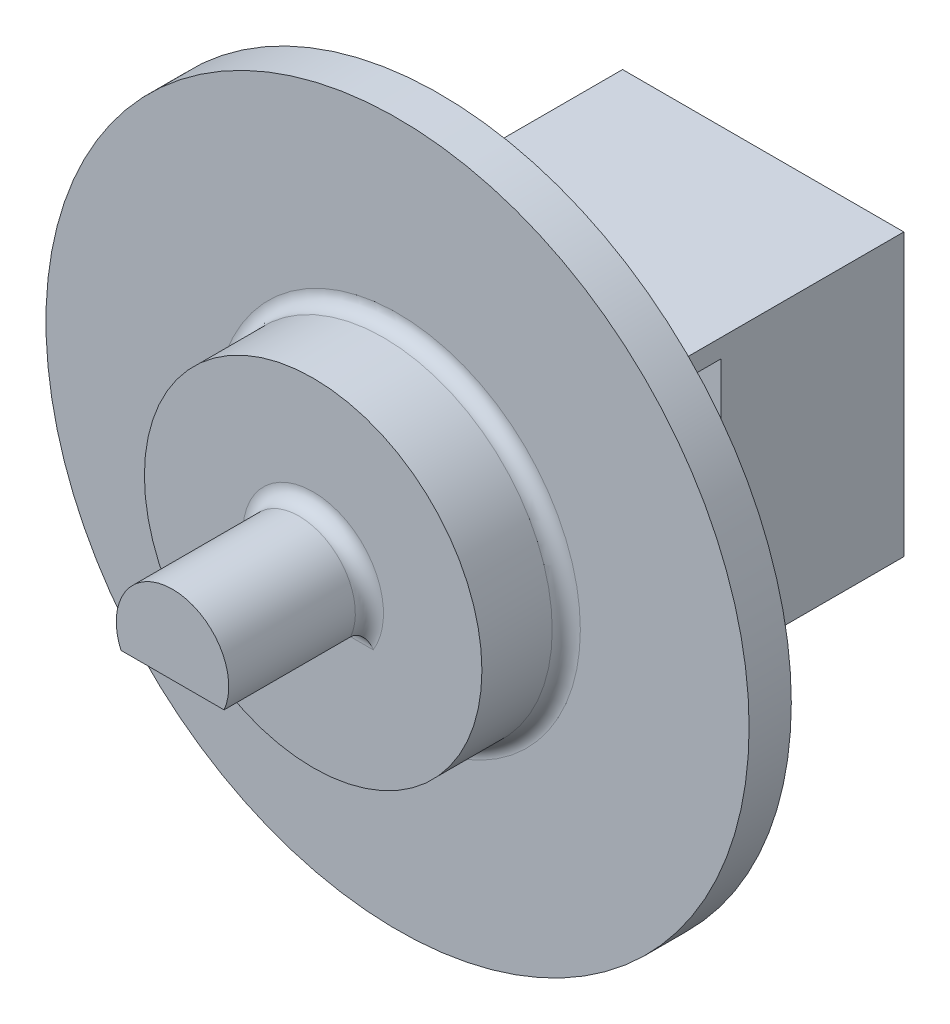
SolidWorks part; units mm, degrees
ref_plane "Front Plane" through (0, 0, 0) normal (0, 0, 1) x (1, 0, 0)
ref_plane "Top Plane" through (0, 0, 0) normal (0, 1, 0) x (1, 0, 0)
ref_plane "Right Plane" through (0, 0, 0) normal (1, 0, 0) x (0, 0, -1)
sketch "Sketch3" plane through (0, 0, 0) normal (0, 0, 1) x (1, 0, 0)
  line L0 (0.8667, 3.2345) -> (0.8667, 5) construction
  line L1 (-5, -5) -> (5, -5)
  line L2 (-5, -5) -> (-5, 5)
  line L3 (-5, 5) -> (5, 5)
  line L4 (5, -5) -> (5, 5)
  line L5 (-5, -5) -> (5, 5) construction
  line L6 (-5, 5) -> (5, -5) construction
  line L7 (3.2345, 0.8667) -> (0.8667, 3.2345)
  line L8 (0.8667, 3.2345) -> (-2.3678, 2.3678)
  line L9 (-2.3678, 2.3678) -> (-3.2345, -0.8667)
  line L10 (-3.2345, -0.8667) -> (-0.8667, -3.2345)
  line L11 (-0.8667, -3.2345) -> (2.3678, -2.3678)
  line L12 (2.3678, -2.3678) -> (3.2345, 0.8667)
  line L13 (3.2345, 0.8667) -> (5, 0.8667) construction
  circle A0 centre (0, 0) radius 1.75
  circle A2 centre (0, 0) radius 2.9 construction
  point P0 (0, 0)
  dimension "D2" = 3.5
  dimension "D3" = 5.8
  dimension "D1" = 10
extrude "Boss-Extrude4" add sketch "Sketch3" along normal blind 11.5 contours L1 L4 L3 L2 | A0 region at (-4.8586, 0, 0) region at (2.7128, -0.7269, 0)
extrude "Cut-Extrude1" cut sketch "Sketch3<3>" against normal blind 5 from surface contours A0 region at (2.7128, -0.7269, 0) starting at face at (0, 0, 11.5)
sketch "Sketch3<3>" plane through (0, 0, 0) normal (0, 0, 1) x (1, 0, 0) same geometry as "Sketch3"
sketch "Sketch4" plane through (0, 0, 11.5) normal (0, 0, 1) x (1, 0, 0)
  line L1 (3.2345, 0.8667) -> (0.8667, 3.2345)
  line L2 (0.8667, 3.2345) -> (-2.3678, 2.3678)
  line L3 (-2.3678, 2.3678) -> (-3.2345, -0.8667)
  line L4 (-3.2345, -0.8667) -> (-0.8667, -3.2345)
  line L5 (-0.8667, -3.2345) -> (2.3678, -2.3678)
  line L6 (2.3678, -2.3678) -> (3.2345, 0.8667)
  circle A0 centre (0, 0) radius 12.5
  circle A3 centre (0, 0) radius 2.9 construction
  dimension "D1" = 25
extrude "Boss-Extrude5" add sketch "Sketch4" along normal blind 1.5
ref_plane "Plane1" through (1.6173, 0.4333, 0) normal (0.9659, 0.2588, 0) x (0, 0, -1)
sketch "Sketch5" plane through (2.9287, -4.4609, 0) normal (0.9659, 0.2588, 0) x (0, 0, 1)
  line L1 (6.5, -7.9669) -> (11.5, -7.9669)
  line L2 (6.5, -7.9669) -> (6.5, -2.1669)
  line L3 (6.5, -2.1669) -> (11.5, -2.1669)
  line L4 (11.5, -7.9669) -> (11.5, -2.1669)
  line L5 (6.5, -7.9669) -> (11.5, -2.1669) construction
  line L6 (6.5, -2.1669) -> (11.5, -7.9669) construction
  line L7 (6.5, -2.1669) -> (13, -2.1669) construction
  line L8 (11.5, 1.0568) -> (11.5, -8.6024) construction
  point P0 (9, -5.0669)
  point P5 (11.5, -2.0669)
  dimension "D2" = 5
extrude "Cut-Extrude2" cut sketch "Sketch5" along normal through all
sketch "Sketch6" plane through (0, 0, 13) normal (0, 0, 1) x (1, 0, 0)
  circle A0 centre (0, 0) radius 6
  dimension "D1" = 12
extrude "Boss-Extrude6" add sketch "Sketch6" along normal blind 3
fillet "Fillet1" radius 0.5 4 edges at (0.7506, -2.8012, 13) (-2.0506, -2.0506, 13) (-2.8012, 0.7506, 13) (-0.7506, 2.8012, 13)
fillet "Fillet2" radius 0.5 1 edges at (6, 0, 13)
sketch "Sketch7" plane through (0, 0, 16) normal (0, 0, 1) x (1, 0, 0)
  line L0 (-1.833, -0.8) -> (1.833, -0.8)
  arc A0 (-1.833, -0.8) -> (1.833, -0.8) centre (0, 0) cw
  dimension "D1" = 2
  dimension "D2" = 0.8
extrude "Boss-Extrude7" add sketch "Sketch7" along normal blind 5
fillet "Fillet3" radius 0.5 2 edges at (0, -0.8, 16) (0, 2, 16)
